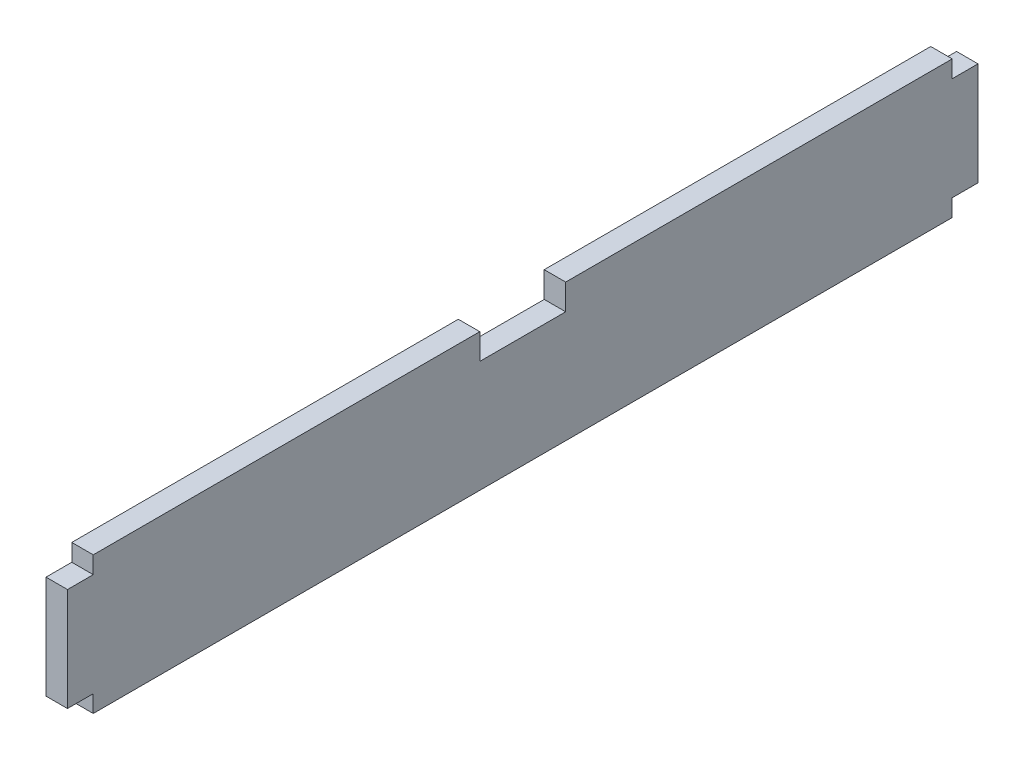
SolidWorks part; units mm, degrees
ref_plane "Front Plane" through (0, 0, 0) normal (0, 0, 1) x (1, 0, 0)
ref_plane "Top Plane" through (0, 0, 0) normal (0, 1, 0) x (1, 0, 0)
ref_plane "Right Plane" through (0, 0, 0) normal (1, 0, 0) x (0, 0, -1)
sketch "Sketch1" plane through (0, 0, 0) normal (0, 0, 1) x (1, 0, 0)
  line L0 (-1.25, -6) -> (-1.25, 6)
  line L1 (-1.25, 8) -> (1.25, 8)
  line L2 (-1.25, 8) -> (-1.25, -8)
  line L3 (-1.25, -8) -> (1.25, -8)
  line L4 (1.25, 8) -> (1.25, -8)
  line L5 (-1.25, 8) -> (1.25, -8) construction
  line L6 (-1.25, -8) -> (1.25, 8) construction
  line L9 (-1.25, 6) -> (1.25, 6)
  line L10 (1.25, -6) -> (-1.25, -6)
  line L11 (1.25, 6) -> (1.25, -6)
  point P0 (0, 0)
  dimension "D1" = 2.5
  dimension "D2" = 16
  dimension "D3" = 12
  dimension "D4" = 6
extrude "Boss-Extrude1" add sketch "Sketch1" along normal blind 100 contours L4 L1 L2 | L2 L3 L4 | L2 L4 region at (0, -7, 0) region at (0, 0, 0) region at (0, 7, 0)
extrude "Boss-Extrude2" add sketch "Sketch1<3>" against normal blind 3 contours L2 L4 region at (0, 0, 0)
sketch "Sketch1<3>" plane through (0, 0, 0) normal (0, 0, 1) x (1, 0, 0) same geometry as "Sketch1"
ref_plane "Plane1" through (0, 0, 50) normal (0, 0, -1) x (-1, 0, 0)
mirror "Mirror1" about plane through (0, 0, 50) normal (0, 0, -1) of "Boss-Extrude2"
sketch "Sketch2" plane through (1.25, 0, 0) normal (1, 0, 0) x (0, 0, -1)
  line L0 (-100, 8) -> (0, 8) construction
  line L1 (-55, 8) -> (-45, 8)
  line L2 (-55, 8) -> (-55, 5)
  line L3 (-55, 5) -> (-45, 5)
  line L4 (-45, 8) -> (-45, 5)
  point P6 (-50, 8)
  point P7 (-50, 8)
  dimension "D1" = 3
  dimension "D2" = 10
extrude "Cut-Extrude1" cut sketch "Sketch2" against normal blind 10
